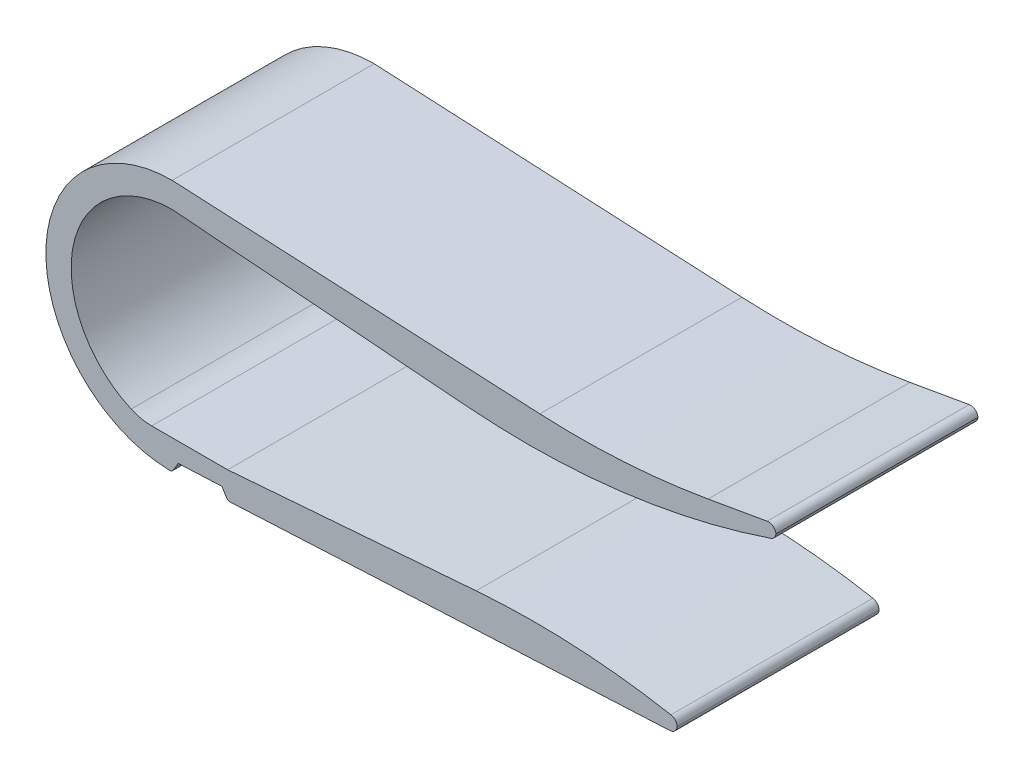
SolidWorks part; units mm, degrees
ref_plane "Front Plane" through (0, 0, 0) normal (0, 0, 1) x (1, 0, 0)
ref_plane "Top Plane" through (0, 0, 0) normal (0, 1, 0) x (1, 0, 0)
ref_plane "Right Plane" through (0, 0, 0) normal (1, 0, 0) x (0, 0, -1)
sketch "Sketch1" plane through (0, 0, 0) normal (0, 0, 1) x (1, 0, 0)
  line L9 (0, 12.5) -> (44.792, 10.2604)
  line L10 (5.5, -12.225) -> (50, -10)
  line L11 (50, -8.75) -> (50, -10)
  line L16 (0, 10) -> (44.792, 6.5)
  line L17 (44.792, -6.5) -> (5.5, -9.5702)
  line L20 (44.792, -6.5) -> (50, -8.75)
  line L21 (44.792, 6.5) -> (59.792, 11.6175)
  line L22 (59.792, 11.6175) -> (59.792, 12.8817)
  line L23 (59.792, 12.8817) -> (44.792, 10.2604)
  line L24 (5.5, -11.5) -> (5.5, -11.25)
  line L26 (0, -12.5) -> (0, -11.5)
  line L28 (5.5, -12.225) -> (5.5, -11.5)
  line L29 (0, -11.5) -> (5.5, -11.25)
  line L30 (5.5, -9.5702) -> (-2.9001, -9.5702)
  arc A1 (0, 12.5) -> (0, -12.5) centre (0, 0) ccw
  arc A2 (0, 10) -> (-2.9001, -9.5702) centre (0, 0) ccw
  dimension "D1" = 0.25
  dimension "D2" = 25
  dimension "D3" = 20
extrude "Boss-Extrude1" add sketch "Sketch1" along normal blind 20
fillet "Fillet2" radius 75 1 edges at (44.792, -6.5, 10)
fillet "Fillet6" radius 75 2 edges at (44.792, 10.2604, 10) (44.792, 6.5, 10)
fillet "Fillet8" radius 0.75 4 edges at (50, -8.75, 10) (50, -10, 10) (59.792, 12.8817, 10) (59.792, 11.6175, 10)
fillet "Fillet11" radius 5 1 edges at (-2.9001, -9.5702, 10)
chamfer "Chamfer2" distance 1 angle 30 2 edges at (5.5, -11.25, 10) (0, -11.5, 10) first distance on face at (5.5, -11.7375, 10) first distance on face at (0, -12, 10)
fillet "Fillet12" radius 0.5 2 edges at (5.486, -12.2257, 10) (0, -12.5, 10)
